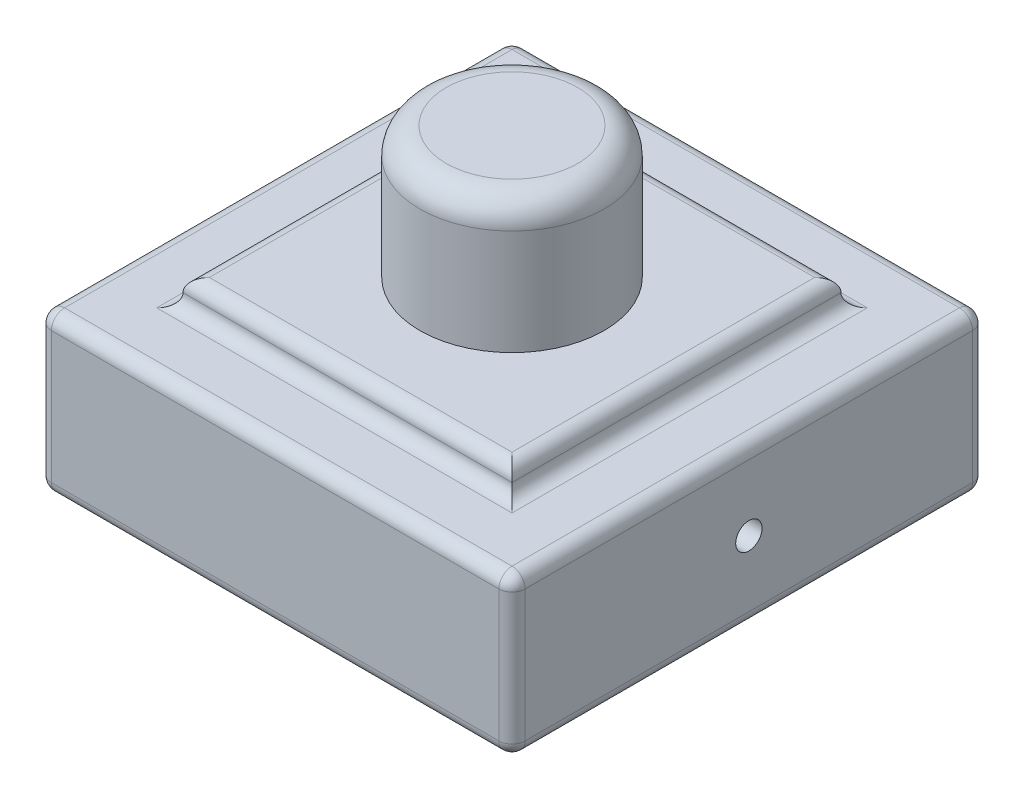
SolidWorks part; units mm, degrees
ref_plane "前视基准面" through (0, 0, 0) normal (0, 0, 1) x (1, 0, 0)
ref_plane "上视基准面" through (0, 0, 0) normal (0, 1, 0) x (1, 0, 0)
ref_plane "右视基准面" through (0, 0, 0) normal (1, 0, 0) x (0, 0, -1)
sketch "草图1" plane through (0, 0, 0) normal (0, 1, 0) x (1, 0, 0)
  line L1 (-18, 18) -> (18, 18)
  line L2 (-18, 18) -> (-18, -18)
  line L3 (-18, -18) -> (18, -18)
  line L4 (18, 18) -> (18, -18)
  line L5 (0, -18) -> (0, 18) construction
  line L6 (-18, 0) -> (18, 0) construction
  point P0 (0, 0)
  dimension "D1" = 36
  dimension "D2" = 36
extrude "凸台-拉伸1" add sketch "草图1" along normal blind 12
sketch "草图2" plane through (0, 12, 0) normal (0, 1, 0) x (1, 0, 0)
  line L1 (-12.5, 12.5) -> (12.5, 12.5)
  line L2 (-12.5, 12.5) -> (-12.5, -12.5)
  line L3 (-12.5, -12.5) -> (12.5, -12.5)
  line L4 (12.5, 12.5) -> (12.5, -12.5)
  line L5 (0, -12.5) -> (0, 12.5) construction
  line L6 (-12.5, 0) -> (12.5, 0) construction
  point P0 (0, 0)
  dimension "D1" = 25
  dimension "D2" = 25
extrude "凸台-拉伸2" add sketch "草图2" along normal blind 2
sketch "草图3" plane through (0, 14, 0) normal (0, 1, 0) x (1, 0, 0)
  circle A0 centre (0, 0) radius 7
  dimension "D1" = 14
extrude "凸台-拉伸3" add sketch "草图3" along normal blind 10
fillet "圆角1" radius 2 1 edges at (0, 24, 7)
fillet "圆角2" radius 1 8 edges at (0, 12, -12.5) (12.5, 12, 0) (0, 12, 12.5) (-12.5, 14, 0) (-12.5, 12, 0) (0, 14, 12.5) (12.5, 14, 0) (0, 14, -12.5)
fillet "圆角3" radius 1 12 edges at (-18, 6, 18) (18, 6, 18) (0, 0, 18) (0, 12, 18) (-18, 12, 0) (0, 12, -18) (18, 12, 0) (-18, 0, 0) (-18, 6, -18) (0, 0, -18) (18, 0, 0) (18, 6, -18)
sketch "草图4" plane through (18, 0, 0) normal (1, 0, 0) x (0, 0, -1)
  line L0 (-18, 6) -> (18, 6) construction
  line L1 (-18, 1) -> (-18, 11) construction
  line L2 (18, 11) -> (18, 1) construction
  line L3 (0, 0) -> (0, 24) construction
  line L4 (5, 24) -> (-5, 24) construction
  circle A0 centre (0, 6) radius 1
  dimension "D1" = 2
extrude "切除-拉伸1" cut sketch "草图4" against normal blind 50
